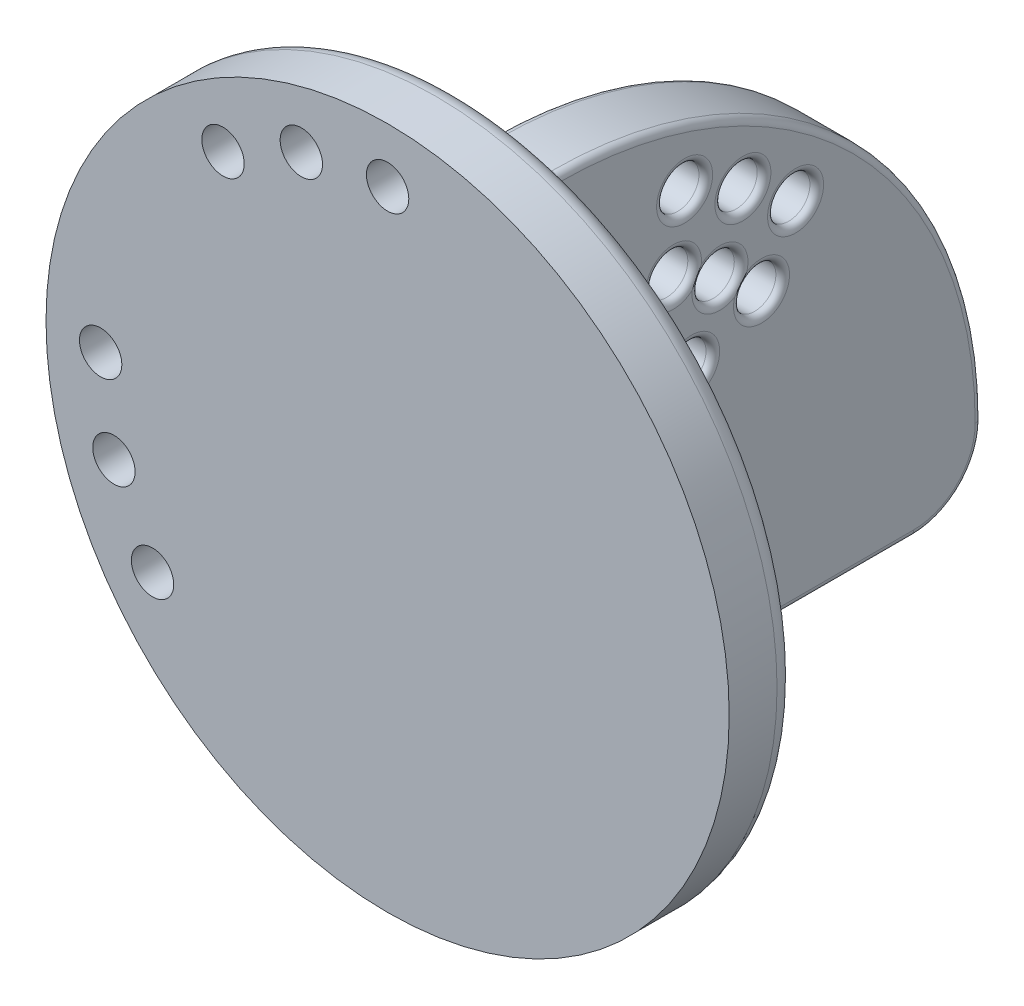
SolidWorks part; units mm, degrees
ref_plane "正面" through (0, 0, 0) normal (0, 0, 1) x (1, 0, 0)
ref_plane "平面" through (0, 0, 0) normal (0, 1, 0) x (1, 0, 0)
ref_plane "右側面" through (0, 0, 0) normal (1, 0, 0) x (0, 0, -1)
sketch "ｽｹｯﾁ1" plane through (0, 0, 0) normal (0, 0, 1) x (1, 0, 0)
  line L0 (0, 0) -> (0, 21) construction
  line L1 (0, 0) -> (-6.3148, 20.0281) construction
  line L2 (0, 0) -> (-6.3148, 20.0281) construction
  line L3 (0, 0) -> (-20.0281, -6.3148) construction
  line L4 (0, 0) -> (0, 21) construction
  line L5 (0, 0) -> (-12.0451, 17.2022) construction
  line L8 (0, 0) -> (0, 21) construction
  line L9 (0, 0) -> (-21, 0) construction
  circle A0 centre (0, 0) radius 25
  circle A1 centre (0, 21) radius 1.55
  circle A2 centre (-20.0281, -6.3148) radius 1.55
  circle A3 centre (-6.3148, 20.0281) radius 1.55
  circle A5 centre (-21, 0) radius 1.55
  circle A8 centre (-17.2022, -12.0451) radius 1.55
  circle A10 centre (-12.0451, 17.2022) radius 1.55
  point P16 (0, 0)
  point P42 (0, 0)
  point P54 (0, 0)
  dimension "D1" = 21
  dimension "D2" = 3.1
  dimension "D3" = 50
  dimension "D5" = 2
  dimension "D6" = 17.5
  dimension "D10" = 35
  dimension "D7" = 90
  dimension "D9" = 2
  dimension "D13" = 2
  dimension "D17" = 2
  dimension "D4" = 2
extrude "ﾎﾞｽ - 押し出し1" add sketch "ｽｹｯﾁ1" along normal blind 5
sketch "ｽｹｯﾁ2" plane through (0, 0, 0) normal (0, 0, 1) x (1, 0, 0)
  line L1 (-2.5, 18) -> (2.5, 18)
  line L2 (-2.5, 18) -> (-2.5, -18)
  line L3 (-2.5, -18) -> (2.5, -18)
  line L4 (2.5, 18) -> (2.5, -18)
  line L5 (-2.5, 18) -> (2.5, -18) construction
  line L6 (-2.5, -18) -> (2.5, 18) construction
  point P0 (0, 0)
  dimension "D1" = 5
  dimension "D2" = 36
sketch "ｽｹｯﾁ3" plane through (0, 0, 0) normal (1, 0, 0) x (0, 0, -1)
  line L0 (0, 0) -> (0, 18)
  line L1 (5, -13) -> (20.5, 13.8468) construction
  line L2 (21.6563, 13.1451) -> (5, -13) construction
  line L3 (0, -18) -> (0, 18) construction
  line L4 (0, 0) -> (0, -18)
  line L5 (0, 18) -> (0, -18) construction
  line L6 (5, -13) -> (16.8206, 5.5546) construction
  line L7 (0, 18) -> (5, 18)
  line L8 (0, 18) -> (0, -18)
  line L9 (0, -18) -> (5, -18)
  line L10 (5, 18) -> (5, -18)
  line L11 (0, -18) -> (36, -18)
  line L12 (0, -18) -> (0, -13)
  line L13 (0, -13) -> (36, -13)
  line L14 (36, -18) -> (36, -13)
  line L15 (5, -13) -> (19.863, 3.2201) construction
  line L16 (5, -13) -> (16.8206, 5.5546) construction
  line L17 (5, -13) -> (13.419, 7.3253) construction
  line L18 (22.7809, 12.3937) -> (5, -13) construction
  line L23 (23.8716, 11.594) -> (5, -13) construction
  arc A0 (5, 18) -> (36, -13) centre (5, -13) cw
  circle A1 centre (5, -13) radius 1.55
  circle A2 centre (18.5, 10.3827) radius 1.55
  circle A3 centre (22.3553, 7.6832) radius 1.55
  circle A4 centre (14.2345, 12.3717) radius 1.55
  circle A5 centre (16.8206, 5.5546) radius 1.55
  circle A6 centre (19.863, 3.2201) radius 1.55
  circle A7 centre (14.7508, 0.9256) radius 1.55
  circle A8 centre (13.419, 7.3253) radius 1.55
  circle A11 centre (12.3051, -3.4798) radius 1.55
  point P23 (5, -13)
  point P25 (5, -13)
  point P42 (5, -13)
  dimension "D4" = 3.1
  dimension "D5" = 3.1
  dimension "D8" = 27
  dimension "D6" = 2
  dimension "D9" = 2.5
  dimension "D10" = 3.1
  dimension "D11" = 22
  dimension "D15" = 3.1
  dimension "D16" = 17
  dimension "D22" = 3.1
  dimension "D23" = 12
  dimension "D1" = 5
  dimension "D2" = 5
  dimension "D3" = 36
  dimension "D7" = 30
  dimension "D12" = 10
  dimension "D13" = 10
  dimension "D14" = 5
  dimension "D21" = 7.5
extrude "ﾎﾞｽ - 押し出し2" add sketch "ｽｹｯﾁ3" along normal mid plane 5 contours A2 L10 A1 L13 A0 | A1 L10 L11 L14 L13 | A1 L13 L8 L9 L10 | A2 L10 L7 L0 L4 L13 A1 region at (0, 2.6829, -2.4773) region at (0, -15.6504, -2.3496) region at (0, -0.2748, -18.3326) region at (0, -15.5227, -20.6829)
fillet "ﾌｨﾚｯﾄ1" radius 0.5 30 edges at (0, -18, 0) (0, 18, 0) (-2.5, 10.3827, -20.05) (-2.5, 8.9203, -26.9203) (-2.5, 18, -2.5) (-2.5, 0, 0) (-2.5, -18, -18) (-2.5, -15.5, -36) (-2.5, -13, -6.55) (2.5, 10.3827, -20.05) (2.5, -18, -18) (2.5, 0, 0) (2.5, 18, -2.5) (2.5, 8.9203, -26.9203) (2.5, -15.5, -36) (2.5, -13, -6.55) (-2.5, 7.6832, -23.9053) (-2.5, 12.3717, -15.7845) (-2.5, 5.5546, -18.3706) (-2.5, 0.9256, -16.3008) (-2.5, -3.4798, -13.8551) (2.5, 7.6832, -23.9053) (2.5, 12.3717, -15.7845) (2.5, 5.5546, -18.3706) (2.5, 0.9256, -16.3008) (2.5, -3.4798, -13.8551) (-2.5, 3.2201, -21.413) (-2.5, 7.3253, -14.969) (2.5, 3.2201, -21.413) (2.5, 7.3253, -14.969)
fillet "ﾌｨﾚｯﾄ2" radius 1.5 1 edges at (25, 0, 0)
fillet "ﾌｨﾚｯﾄ3" radius 5 3 edges at (-2.3536, -17.8536, -35.8536) (2.3536, -17.8536, -35.8536) (0, -18, -36)
